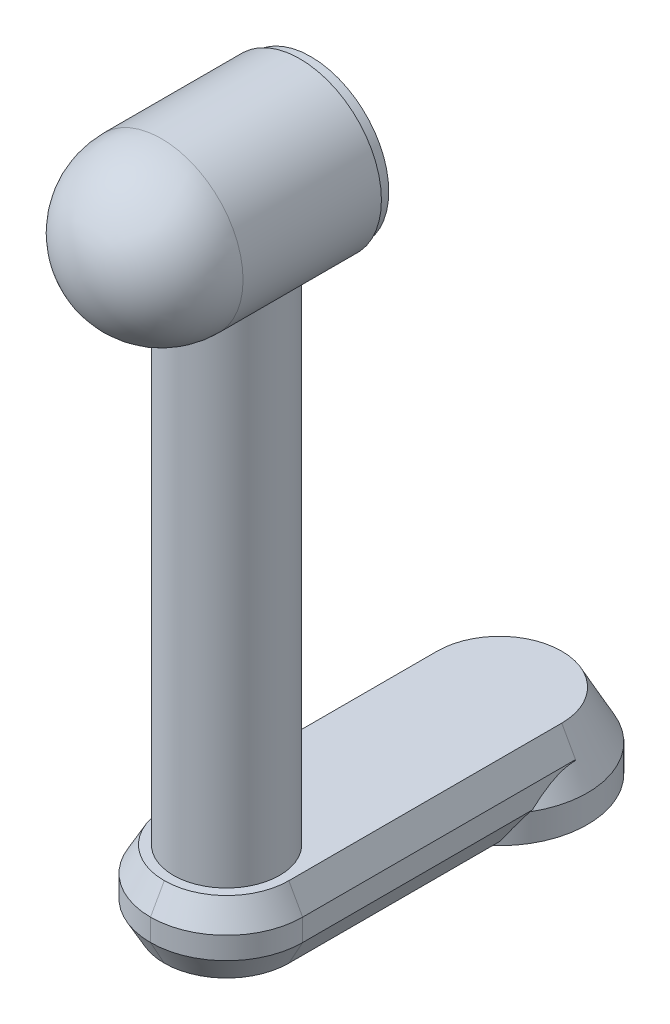
SolidWorks part; units mm, degrees
note: '?' marks a value the reader was unsure of.
material "2014-T4"
ref_plane "Front Plane" through (0, 0, 0) normal (0, 0, 1) x (1, 0, 0)
ref_plane "Top Plane" through (0, 0, 0) normal (0, 1, 0) x (1, 0, 0)
ref_plane "Right Plane" through (0, 0, 0) normal (1, 0, 0) x (0, 0, -1)
sketch "Sketch1" plane through (0, 0, 0) normal (0, 1, 0) x (1, 0, 0)
  circle A0 centre (0, 0) radius 48
  dimension "D1" = 96
extrude "Boss-Extrude1" add sketch "Sketch1" along normal blind 41
chamfer "Chamfer1" distance 26 distance2 14 1 edges at (0, 41, 48) first distance on face at (0, 41, 48)
sketch "Sketch2" plane through (0, 0, 0) normal (0, -1, 0) x (1, 0, 0)
  circle A0 centre (0, 0) radius 30
  dimension "D1" = 60
extrude "Boss-Extrude2" add sketch "Sketch2" along normal blind 1
sketch "Sketch3" plane through (0, 0, 0) normal (0, 0, 1) x (1, 0, 0)
  line L0 (34, 41) -> (-34, 41) construction
  line L1 (41.5, 41) -> (-41.5, 41)
  line L2 (41.5, 41) -> (41.5, 2)
  line L3 (41.5, 2) -> (-41.5, 2)
  line L4 (-41.5, 41) -> (-41.5, 2)
  dimension "D1" = 39
  dimension "D2" = 83
  dimension "D3" = 41.5
extrude "Boss-Extrude3" add sketch "Sketch3" along normal blind 190.4
fillet "Fillet1" radius 41.5 2 edges at (-41.5, 21.5, 190.4) (41.5, 21.5, 190.4)
chamfer "Chamfer2" distance 7.5 distance2 13.5 4 edges at (-41.5, 2, 86.5097) (-29.3449, 2, 178.2449) (29.3449, 2, 178.2449) (41.5, 2, 86.5097) first distance on face at (0, 2, 115.5019)
chamfer "Chamfer3" distance 13.5 distance2 7.5 4 edges at (41.5, 41, 74.45) (-41.5, 41, 74.45) (29.3449, 41, 178.2449) (-29.3449, 41, 178.2449) first distance on face at (41.5, 28.9426, 63.3533) first distance on face at (-41.5, 28.9426, 63.3533) first distance on face at (25.0475, 28.25, 173.9475) first distance on face at (-25.0475, 28.25, 173.9475)
sketch "Sketch4" plane through (0, 41, 0) normal (0, 1, 0) x (1, 0, 0)
  arc A0 (-34, -148.9) -> (0, -182.9) centre (0, -148.9) ccw construction
  arc A1 (-34, -148.9) -> (0, -182.9) centre (0, -148.9) ccw
  circle A2 centre (0, -148.9) radius 29
  dimension "D1" = 58
extrude "Boss-Extrude4" add sketch "Sketch4" along normal blind 306.9 contours A2
ref_axis "Axis1" through (0, 347.9, 148.9) along (0, -1, 0)?
ref_plane "Plane1" through (0, 0, 148.9) normal (0, 0, 1) x (1, 0, 0)
sketch "Sketch6" plane through (0, 0, 148.9) normal (0, 0, 1) x (1, 0, 0)
  line L0 (0, 347.9) -> (0, 41) construction
  line L1 (29, 347.9) -> (-29, 347.9) construction
  line L2 (29, 347.9) -> (-29, 347.9) construction
  circle A0 centre (0, 347.9) radius 44.5
  dimension "D1" = 89
extrude "Boss-Extrude5" add sketch "Sketch6" along normal blind 80 and the other way blind 40
fillet "Fillet2" radius 44.5 1 edges at (44.5, 347.9, 228.9)
sketch "Sketch7" plane through (0, 2, 0) normal (0, -1, 0) x (1, 0, 0)
  circle A0 centre (0, 148.9) radius 24
  circle A1 centre (0, 148.9) radius 29 construction
  circle A2 centre (0, 148.9) radius 29
  dimension "D1" = 5
extrude "Cut-Extrude1" cut sketch "Sketch7" against normal blind 330 contours A0
sketch "Sketch8" plane through (0, 0, 108.9) normal (0, 0, -1) x (-1, 0, 0)
  circle A0 centre (0, 347.9) radius 39.5
  circle A1 centre (0, 347.9) radius 44.5 construction
  dimension "D1" = 5
extrude "Cut-Extrude2" cut sketch "Sketch8" along a picked direction on the side against the normal blind 80
sketch "Sketch9" plane through (0, 2, 0) normal (0, -1, 0) x (1, 0, 0)
  circle A0 centre (0, 148.9) radius 24
extrude "Boss-Extrude6" add sketch "Sketch9" against normal blind 5
sketch "Sketch10" plane through (0, 0, 108.9) normal (0, 0, -1) x (-1, 0, 0)
  circle A0 centre (0, 347.9) radius 42.5
  dimension "D1" = 85
extrude "Boss-Extrude7" add sketch "Sketch10" along normal blind 6
